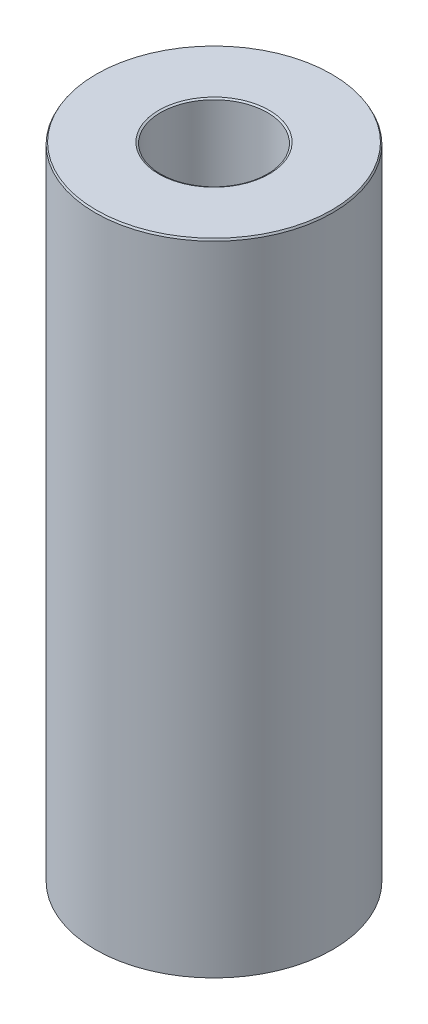
SolidWorks part; units mm, degrees
ref_plane "Front Plane" through (0, 0, 0) normal (0, 0, 1) x (1, 0, 0)
ref_plane "Top Plane" through (0, 0, 0) normal (0, 1, 0) x (1, 0, 0)
ref_plane "Right Plane" through (0, 0, 0) normal (1, 0, 0) x (0, 0, -1)
sketch "Sketch1" plane through (0, 0, 0) normal (0, 1, 0) x (1, 0, 0)
  circle A0 centre (0, 0) radius 30
  dimension "SLEEVE_OD" = 60
extrude "Boss-Extrude1" add sketch "Sketch1" along normal blind 161.9335
sketch "Sketch2" plane through (0, 0, 0) normal (0, 1, 0) x (1, 0, 0)
  circle A0 centre (0, 0) radius 13.4869
  dimension "BORE_D" = 26.9737
extrude "Cut-Extrude1" cut sketch "Sketch2" along normal through all
chamfer "Chamfer1" distance 0.4726 angle 28.726 4 edges at (0, 161.9335, 13.4869) (0, 0, 13.4869) (0, 0, 30) (0, 161.9335, 30) first distance on face at (0, 161.9335, 13.4869) first distance on face at (0, 0, 13.4869) first distance on face at (0, 161.9335, 30)
